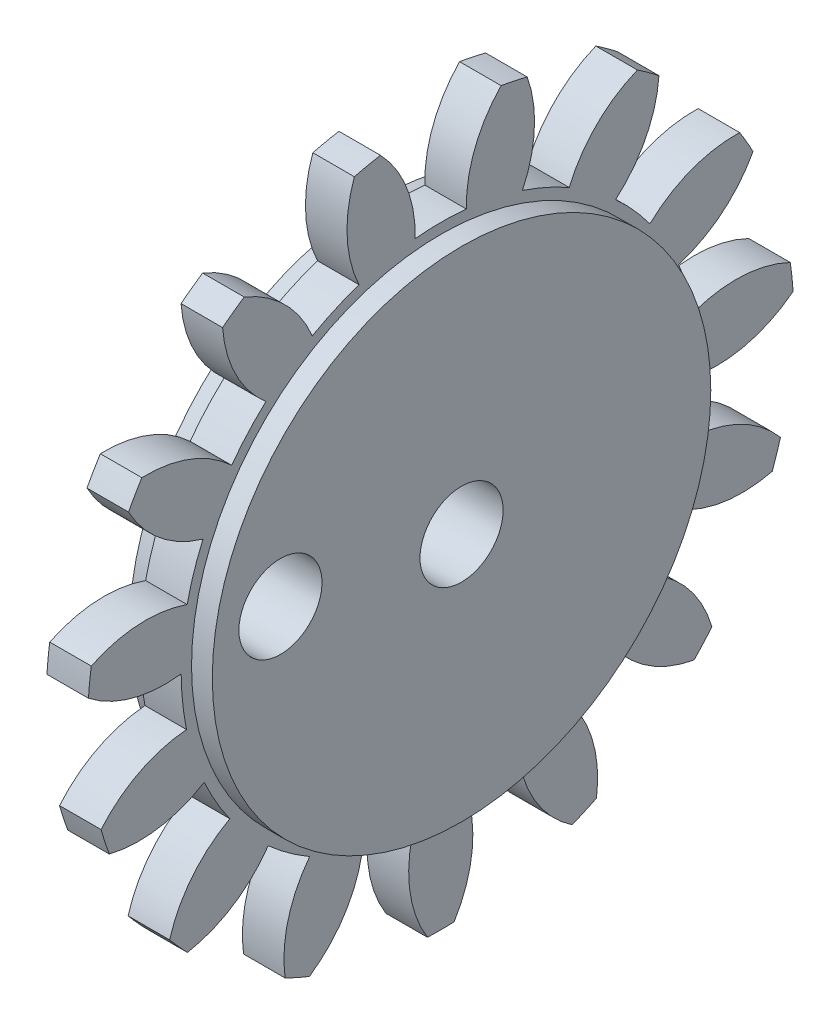
SolidWorks part; units mm, degrees
ref_plane "Plane1" through (0, 0, 0) normal (0, 0, 1) x (1, 0, 0)
ref_plane "Plane2" through (0, 0, 0) normal (0, 1, 0) x (1, 0, 0)
ref_plane "Plane3" through (0, 0, 0) normal (1, 0, 0) x (0, 0, -1)
other "Configuration Table"
sketch "HoldingSke" plane through (0, 0, 0) normal (0, 1, 0) x (1, 0, 0)
  line L0 (0, 0) -> (98.1381, -26.296)
  line L1 (-15, 0) -> (100, 0) construction
  line L2 (0, 0) -> (-2.1039, 2.3779)
  line L3 (0, 0) -> (-11.863, 4.5341)
  line L4 (0, 0) -> (8.3417, 2.2352)
  line L5 (0, 0) -> (-11.8993, -4.4381)
  line L6 (0, 0) -> (-5.2639, -3.5516)
  line L7 (-2.1039, 2.3779) -> (0.6298, 14.7802)
  line L8 (-76.2, 54.61) -> (-61.976, 54.61)
  line L9 (-67.7845, 28.3722) -> (-49.3413, 33.142)
  line L10 (-76.2, 71.12) -> (104.1128, 71.12)
  line L11 (0, 0) -> (-6.35, 0)
  line L12 (-76.2, 101.6) -> (-75.9714, 101.6)
  line L13 (24.9733, 27.94) -> (52.9518, 28.4284)
  line L14 (24.9733, 27.94) -> (24.9746, 27.94)
  line L15 (24.9733, 27.94) -> (100.4006, 29.5858)
  circle A0 centre (0, 0) radius 6.35
  circle A1 centre (0, 0) radius 38.1
  circle A2 centre (0, 0) radius 38.1
  circle A3 centre (0, 0) radius 6.35
  dimension "Num_teeth" = 15
  dimension "H" = 19.05
  dimension "Pitch_radius" = 180.3128
  dimension "Width" = 6.35
  dimension "Thickness" = 6.35
sketch "BasProSke" plane through (0, 0, 0) normal (0, 1, 0) x (1, 0, 0)
  line L0 (-10, 0) -> (60, 0) construction
  line L1 (0, 0) -> (0, 53.975)
  line L2 (0, 0) -> (6.35, 0)
  line L3 (6.35, 0) -> (6.35, 53.975)
  line L4 (6.35, 53.975) -> (0, 53.975)
  dimension "Thickness" = 6.35
  dimension "Diameter" = 107.95
revolve "Base-Revolve" add sketch "BasProSke" angle 360 about L0
sketch "TooCutSke" plane through (0, 0, 0) normal (1, 0, 0) x (0, 0, -1)
  line L1 (0, 0) -> (0, 107) construction
  line L2 (0, 0) -> (-5.3779, 47.3204) construction
  line L3 (0, 0) -> (-19.7119, 92.7371) construction
  line L4 (-5.3779, 47.3204) -> (-9.8559, 46.3685) construction
  arc A0 (3.9155, 39.4926) -> (-3.9155, 39.4926) centre (0, 0) ccw
  arc A1 (9.2414, 53.2038) -> (-9.2414, 53.2038) centre (0, 0) ccw
  circle A2 centre (0, 0) radius 47.625 construction
  circle A3 centre (0, 0) radius 46.108 construction
  arc A4 (-3.9155, 39.4926) -> (-9.2414, 53.2038) centre (-22.9591, 39.9854) ccw
  arc A5 (9.2414, 53.2038) -> (3.9155, 39.4926) centre (22.9591, 39.9854) ccw
extrude "ToothCut" cut sketch "TooCutSke" along normal through all
fillet "Breaks" [suppressed] radius 0.127 tangent propagation no
fillet "RootFillets" [suppressed] radius 1.5888
pattern_circular "TeethCuts" count 15 every 24 about axis through (-10, 0, 0) along (1, 0, 0) of "ToothCut", "RootFillets", "Breaks"
sketch "HubNeaOneSke" plane through (0, 0, 0) normal (-1, 0, 0) x (0, 0, 1)
  circle A0 centre (0, 0) radius 38.1
  dimension "Diameter" = 76.2
extrude "HubNearOne" [suppressed] add sketch "HubNeaOneSke" along normal blind 6.3501
sketch "HubNeaBotSke" plane through (0, 0, 0) normal (-1, 0, 0) x (0, 0, 1)
  circle A0 centre (0, 0) radius 38.1
  dimension "Diameter" = 76.2
extrude "HubNearBoth" add sketch "HubNeaBotSke" along normal blind 3.175
ref_plane "FarPln" through (6.35, 0, 0) normal (1, 0, 0) x (0, 0, -1)
sketch "HubFarSke" plane through (6.35, 0, 0) normal (1, 0, 0) x (0, 0, -1)
  circle A0 centre (0, 0) radius 38.1
  dimension "Diameter" = 76.2
extrude "HubFar" add sketch "HubFarSke" along normal blind 3.175
sketch "BorSke" plane through (0, 0, 0) normal (1, 0, 0) x (0, 0, -1)
  circle A0 centre (0, 0) radius 6.35
  dimension "Diameter" = 12.7
extrude "Bore" cut sketch "BorSke" along normal mid plane 25.4001
sketch "KeySke" plane through (0, 0, 0) normal (1, 0, 0) x (0, 0, -1)
  line L0 (-1.5875, 0) -> (-1.5875, 7.874)
  line L1 (-1.5875, 7.874) -> (1.5875, 7.874)
  line L2 (1.5875, 7.874) -> (1.5875, 0)
  line L3 (0, 0) -> (0, 34) construction
  line L4 (-1.5875, 0) -> (1.5875, 0)
  dimension "Width" = 3.175
extrude "Keyway" [suppressed] cut sketch "KeySke" along normal mid plane 25.4001
pattern_circular "Keyway2" [suppressed] count 2 every 90 about axis through (-10, 0, 0) along (1, 0, 0) reverse direction yes
sketch "Sketch1" plane through (-3.175, 0, 0) normal (-1, 0, 0) x (0, 0, 1)
  line L0 (0, 0) -> (27.6826, 4.2691) construction
  line L1 (0, 0) -> (46.7437, 26.9875) construction
  circle A0 centre (27.6826, 4.2691) radius 6.35
  arc A1 (47.7296, 25.2029) -> (45.6911, 28.7336) centre (0, 0) ccw construction
  circle A2 centre (0, 0) radius 28.0098 construction
  circle A3 centre (24.2572, 14.0049) radius 6.35 construction
  dimension "D1" = 12.7
extrude "Cut-Extrude1" cut sketch "Sketch1" against normal through all
equation "' \"Pitch@HoldingSke\" = 4"
equation "' \"Num_teeth@HoldingSke\" = 12"
equation "' \"Ap@HoldingSke\" =  20"
equation "' \"Ap@HoldingSke\" = 20"
equation "' \"Width@HoldingSke\" = 0.5"
equation "' \"Hub_dia@HoldingSke\"= 1"
equation "' \"Hub_dia@HoldingSke\" = 1"
equation "' \"Overall_len@HoldingSke\" = 1.0"
equation "' \"Bore@HoldingSke\" = 0.75"
equation "' \"T_dim@HoldingSke\" = 0.85"
equation "' \"Width@KeySke\" = 0.25"
equation "' \"Show_teeth@HoldingSke\" = 13"
equation "' \"Backlash@HoldingSke\" = 0.009"
equation "' \"Addendum_fac@HoldingSke\" = 1.0"
equation "' \"Dedendum_fac@HoldingSke\" = 1.25"
equation "' \"Dedendum_add@HoldingSke\" = 0.00005"
equation "' \"Clearance_fac@HoldingSke\" = 0.25"
equation "' \"Pitch@HoldingSke\" = 0.5"
equation "' \"Num_teeth@HoldingSke\" = 23"
equation "' \"Show_teeth@HoldingSke\" = 23"
equation "' \"Backlash@HoldingSke\" = 0.0375"
equation "\"Overcut_dia@TooCutSke\" = (\"Num_teeth@HoldingSke\" + 2 * \"Addendum_fac@HoldingSke\") / \"Pitch@HoldingSke\" + 0.002"
equation "\"Pitch_dia@TooCutSke\" = \"Num_teeth@HoldingSke\" / \"Pitch@HoldingSke\""
equation "\"Base_dia@TooCutSke\" = \"Num_teeth@HoldingSke\" / \"Pitch@HoldingSke\" * cos((\"Ap@HoldingSke\"  * 3.14159265 / 180))"
equation "\"Root_dia@TooCutSke\" = (\"Num_teeth@HoldingSke\" + 2) / \"Pitch@HoldingSke\" - 2 * (\"Addendum_fac@HoldingSke\" + \"Dedendum_fac@HoldingSke\") / \"Pitch@HoldingSke\" - \"Dedendum_add@HoldingSke\" * 2"
equation "\"Half_ang@TooCutSke\" = 180 / \"Num_teeth@HoldingSke\""
equation "\"Half_CT@TooCutSke\" = \"Num_teeth@HoldingSke\" / \"Pitch@HoldingSke\" * sin((3.14159265 / 2 / \"Num_teeth@HoldingSke\")) / 2 - 7 * \"Backlash@HoldingSke\" / 4"
equation "\"Flank_rad@TooCutSke\" = \"Num_teeth@HoldingSke\" / \"Pitch@HoldingSke\" / 5"
equation "\"Radius@RootFillets\" = \"Clearance_fac@HoldingSke\" / \"Pitch@HoldingSke\" + \"Dedendum_add@HoldingSke\""
equation "\"Break_rad@Breaks\" = 0.02 / \"Pitch@HoldingSke\""
equation "\"Thickness@HoldingSke\" = \"Width@HoldingSke\""
equation "\"OAL@HoldingSke\" = \"Thickness@HoldingSke\""
equation "\"MHD@HoldingSke\" = (\"Num_teeth@HoldingSke\" + 2) / \"Pitch@HoldingSke\" - 2 * (\"Addendum_fac@HoldingSke\" + \"Dedendum_fac@HoldingSke\")  / \"Pitch@HoldingSke\" - \"Dedendum_add@HoldingSke\" * 2"
equation "\"MBD@HoldingSke\" = (\"Num_teeth@HoldingSke\" + 2) / \"Pitch@HoldingSke\" - 2 * (\"Addendum_fac@HoldingSke\" + \"Dedendum_fac@HoldingSke\")  / \"Pitch@HoldingSke\" - \"Dedendum_add@HoldingSke\" * 2 - 0.002"
equation "\"MHD@HoldingSke\" = ((sgn( \"MHD@HoldingSke\" - \"Hub_dia@HoldingSke\" )-1)*( \"MHD@HoldingSke\" - \"Hub_dia@HoldingSke\" ))/-2+ \"Hub_dia@HoldingSke\""
equation "\"MBD@HoldingSke\" = ((sgn( \"MBD@HoldingSke\" - \"Bore@HoldingSke\" )-1)*( \"MBD@HoldingSke\" - \"Bore@HoldingSke\" ))/-2+ \"Bore@HoldingSke\""
equation "\"OAL@HoldingSke\" = ((sgn( \"OAL@HoldingSke\" - \"Overall_len@HoldingSke\" )+1)*( \"OAL@HoldingSke\" - \"Overall_len@HoldingSke\" ))/2 + \"Overall_len@HoldingSke\" + 0.000002"
equation "\"Num_teeth@TeethCuts\" = int( \"Show_teeth@HoldingSke\" ) + 1"
equation "\"Num_teeth@TeethCuts\" = ((sgn( \"Num_teeth@TeethCuts\" - \"Num_teeth@HoldingSke\" )-1)*( \"Num_teeth@TeethCuts\" - \"Num_teeth@HoldingSke\" ))/-2+ \"Num_teeth@HoldingSke\""
equation "\"Num_teeth@TeethCuts\" = ((sgn( \"Num_teeth@TeethCuts\" - 2.0)+1)*( \"Num_teeth@TeethCuts\" - 2.0))/2 +2.0"
equation "\"Angle@TeethCuts\" = 360.0 / \"Num_teeth@HoldingSke\""
equation "\"Diameter@BasProSke\" = (\"Num_teeth@HoldingSke\" + 2 * \"Addendum_fac@HoldingSke\") / \"Pitch@HoldingSke\""
equation "\"Thickness@BasProSke\"  = \"Thickness@HoldingSke\""
equation "' \"Fillet_rad@BasProSke\" =  \"Thickness@HoldingSke\" * 0.05"
equation "' \"Fillet_rad@BasProSke\" = \"Thickness@HoldingSke\" * 0.05"
equation "\"MHD@HoldingSke\" = ((sgn( \"MHD@HoldingSke\" - \"Root_dia@TooCutSke\" )-1)*( \"MHD@HoldingSke\" - \"Root_dia@TooCutSke\" ))/-2+ \"Root_dia@TooCutSke\""
equation "\"Diameter@HubNeaOneSke\" = \"MHD@HoldingSke\""
equation "\"Length@HubNearOne\" = \"OAL@HoldingSke\" - \"Thickness@BasProSke\""
equation "\"Diameter@HubNeaBotSke\" = \"MHD@HoldingSke\""
equation "\"Length@HubNearBoth\" = ( \"OAL@HoldingSke\" - \"Thickness@BasProSke\" ) / 2.0"
equation "\"Thickness@FarPln\" = \"Thickness@BasProSke\""
equation "\"Diameter@HubFarSke\" = \"MHD@HoldingSke\""
equation "\"Length@HubFar\" = ( \"OAL@HoldingSke\" - \"Thickness@BasProSke\" ) / 2.0"
equation "\"Diameter@BorSke\" = \"MBD@HoldingSke\""
equation "\"D1@Bore\" = \"OAL@HoldingSke\" * 2.0"
equation "\"D1@Keyway\" = \"OAL@HoldingSke\" * 2.0"
equation "\"Offset@KeySke\" = \"T_dim@HoldingSke\" - \"MBD@HoldingSke\" / 2.0"
